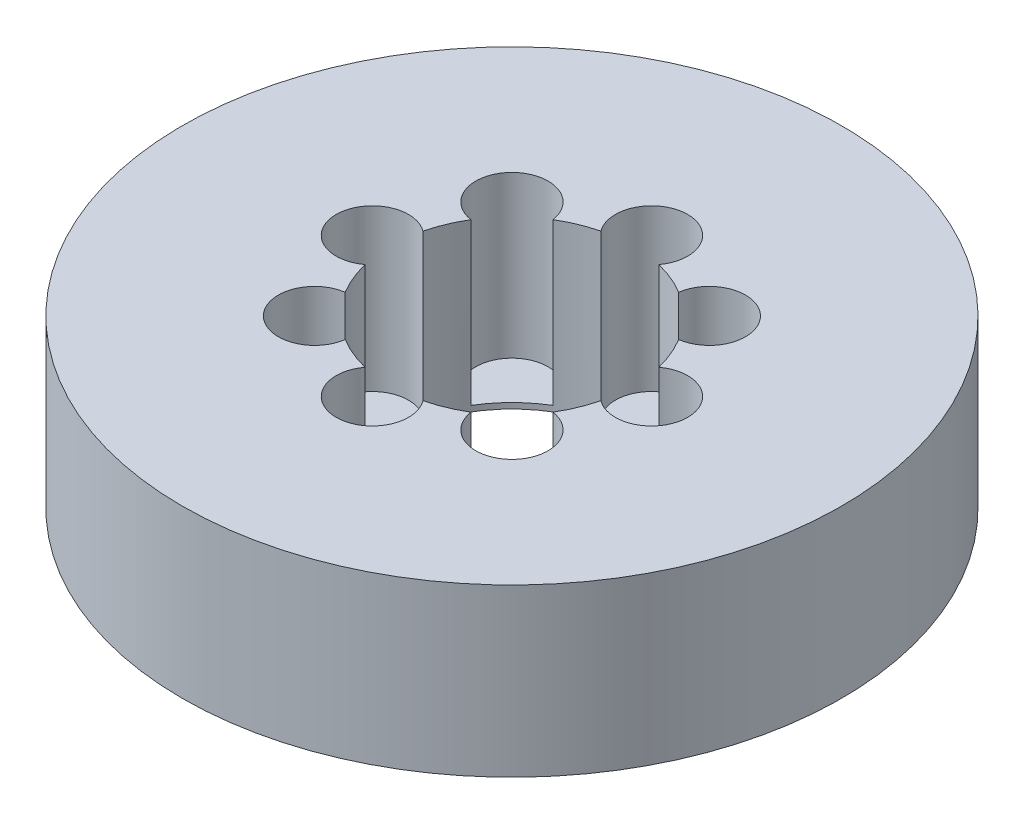
SolidWorks part; units mm, degrees
ref_plane "Front Plane" through (0, 0, 0) normal (0, 0, 1) x (1, 0, 0)
ref_plane "Top Plane" through (0, 0, 0) normal (0, 1, 0) x (1, 0, 0)
ref_plane "Right Plane" through (0, 0, 0) normal (1, 0, 0) x (0, 0, -1)
sketch "Sketch1" plane through (0, 0, 0) normal (0, 1, 0) x (1, 0, 0)
  circle A0 centre (0, 0) radius 47.5
  dimension "FLANGE_OD" = 95
extrude "Boss-Extrude1" add sketch "Sketch1" along normal blind 24
sketch "Sketch2" plane through (0, 0, 0) normal (0, 1, 0) x (1, 0, 0)
  circle A0 centre (0, 0) radius 17.5
  dimension "BORE_D" = 35
extrude "Cut-Extrude1" cut sketch "Sketch2" along normal through all
sketch "Sketch3" plane through (0, 24, 0) normal (0, 1, 0) x (1, 0, 0)
  circle A0 centre (0, 0) radius 20.1182 construction
  circle A1 centre (-20.1182, 0) radius 5.2146
  dimension "BOLT_D" = 10.4293
  dimension "BOLT_PCD" = 40.2365
extrude "Cut-Extrude2" cut sketch "Sketch3" against normal blind 23.1834
pattern_circular "CirPattern1" count 8 over 360 about axis through (0, 0, 0) along (0, 1, 0) of "Cut-Extrude2"
